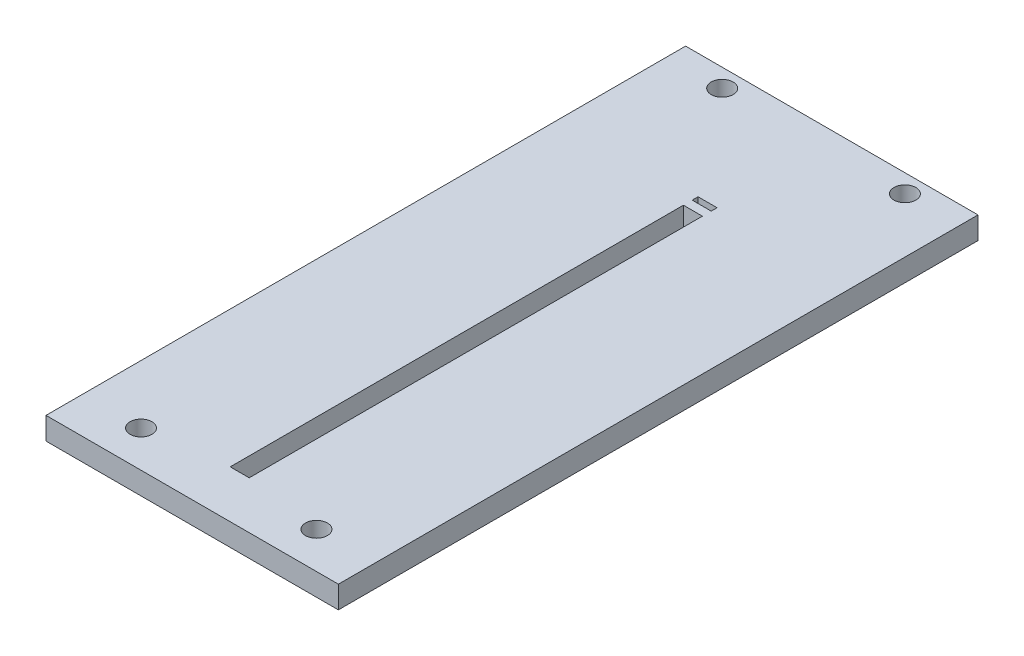
SolidWorks part; units mm, degrees
ref_plane "Front Plane" through (0, 0, 0) normal (0, 0, 1) x (1, 0, 0)
ref_plane "Top Plane" through (0, 0, 0) normal (0, 1, 0) x (1, 0, 0)
ref_plane "Right Plane" through (0, 0, 0) normal (1, 0, 0) x (0, 0, -1)
sketch "Sketch1" plane through (0, 0, 0) normal (0, 1, 0) x (1, 0, 0)
  line L1 (-20, 0) -> (20, 0)
  line L2 (-20, 0) -> (-20, 87.5)
  line L3 (-20, 87.5) -> (20, 87.5)
  line L4 (20, 0) -> (20, 87.5)
  point P5 (0, 0)
  dimension "D1" = 40
  dimension "D2" = 87.5
extrude "Boss-Extrude1" add sketch "Sketch1" along normal blind 3.05 contours L2 | L1 L4 L3 L2 | L4 region at (0, 0, -43.75)
sketch "Sketch4" plane through (0, 3.05, 0) normal (0, 1, 0) x (1, 0, 0)
  line L0 (-20, 87.5) -> (20, 87.5) construction
  line L2 (-20, 0) -> (20, 0) construction
  line L3 (1.3, 70.5) -> (-1.3, 70.5)
  line L4 (-1.3, 70.5) -> (-1.3, 69.7)
  line L5 (-1.3, 69.7) -> (1.3, 69.7)
  line L6 (1.3, 69.7) -> (1.3, 70.5)
  line L7 (0, 0) -> (0, 87.5) construction
  line L9 (1.3, 68.5) -> (-1.3, 68.5)
  line L10 (-1.3, 68.5) -> (-1.3, 6.5)
  line L11 (-1.3, 6.5) -> (1.3, 6.5)
  line L12 (1.3, 6.5) -> (1.3, 68.5)
  point P6 (0, 6.5)
  point P10 (0, 70.5)
  point P22 (0, 68.5)
  dimension "D1" = 17
  dimension "D2" = 0.8
  dimension "D3" = 1.2
  dimension "D4" = 2.6
  dimension "D7" = 6.5
extrude "Cut-Extrude1" cut sketch "Sketch4" against normal through all contours L5 L7 L3 L4 | L11 L7 L9 L10 | L7 L11 L12 L9 | L7 L5 L6 L3 | L6 L3 L4 L5 region at (0.65, 3.05, -70.1) region at (0.65, 3.05, -37.5) region at (-0.65, 3.05, -37.5) region at (-0.65, 3.05, -70.1)
sketch "Sketch7" plane through (0, 3.05, 0) normal (0, 1, 0) x (1, 0, 0)
  line L0 (0, 0) -> (-12, 0)
  line L1 (-20, 0) -> (20, 0) construction
  line L2 (-12, 0) -> (-12, 5)
  line L4 (0, 0) -> (0, 70) construction
  circle A0 centre (-12, 5) radius 1.5
  circle A2 centre (12, 5) radius 1.5
  dimension "D3" = 3
  dimension "D1" = 12
  dimension "D2" = 5
extrude "Cut-Extrude4" cut sketch "Sketch7" against normal through all contours A0 L2 | L2 A0 | A2 region at (-10.9693, 3.05, -3.9693)
hole_wizard "Ø3.0mm Dowel Hole1" positions "Sketch8" profile "Sketch9" hole size "Ø3.0" standard "ANSI Metric" end condition through all
sketch "Sketch8" plane through (0, 3.05, 0) normal (0, 1, 0) x (1, 0, 0)
  line L0 (0, 87.5332) -> (0, 2.5332) construction
  line L3 (-20, 87.5) -> (20, 87.5) construction
  point P0 (-12.5, 85)
  point P2 (12.5, 85)
  dimension "D1" = 12.5
  dimension "D2" = 2.5
sketch "Sketch9" plane through (-12.5, 3.05, -85) normal (1, 0, 0) x (0, 0, 1)
  line L0 (0, 0) -> (0, 3.05)
  line L1 (0, 3.05) -> (1.5, 3.05)
  line L2 (1.5, 3.05) -> (1.5, 0)
  line L5 (1.5, 0) -> (0, 0)
  line L11 (0, -6.35) -> (0, 107.95) construction
  dimension "Thru Hole Dia." = 3
  dimension "Thru Hole Depth" = 3.05
